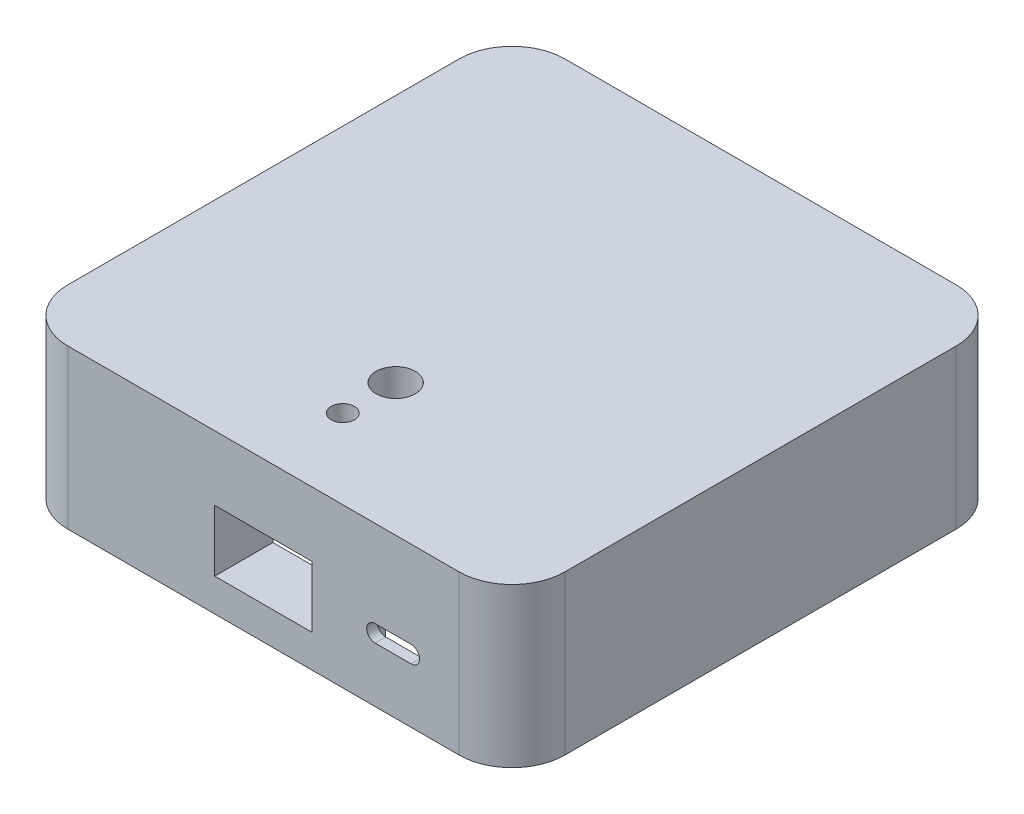
SolidWorks part; units mm, degrees
other "标注1"
sketch "草图24" plane through (-42, 0, -42) normal (-0.1821, -0.7006, -0.6899) x (-0.9631, -0.0142, 0.2687)
ref_plane "前视基准面" through (0, 0, 0) normal (0, 0, 1) x (1, 0, 0)
ref_plane "上视基准面" through (0, 0, 0) normal (0, 1, 0) x (1, 0, 0)
ref_plane "右视基准面" through (0, 0, 0) normal (1, 0, 0) x (0, 0, -1)
sketch "草图1" plane through (0, 0, 0) normal (0, 1, 0) x (1, 0, 0)
  line L1 (47, 47) -> (-47, 47)
  line L2 (47, 47) -> (47, -47)
  line L3 (47, -47) -> (-47, -47)
  line L4 (-47, 47) -> (-47, -47)
  line L5 (47, 47) -> (-47, -47) construction
  line L6 (47, -47) -> (-47, 47) construction
  point P0 (0, 0)
  dimension "D1" = 94
extrude "凸台-拉伸1" add sketch "草图1" along normal blind 30
fillet "圆角1" radius 10 4 edges at (47, 15, 47) (47, 15, -47) (-47, 15, -47) (-47, 15, 47)
shell "抽壳1" thickness 2 removed face at (0, 0, 0)
sketch "草图2" plane through (0, 0, 47) normal (0, 0, 1) x (1, 0, 0)
  line L0 (-37, 30) -> (37, 30) construction
  line L1 (-12.05, 30) -> (12.05, 30)
  line L2 (-12.05, 30) -> (-12.05, 0)
  line L3 (-12.05, 0) -> (12.05, 0)
  line L4 (12.05, 30) -> (12.05, 0)
  line L5 (-12.05, 30) -> (12.05, 0) construction
  line L6 (-12.05, 0) -> (12.05, 30) construction
  line L8 (0, 0) -> (0, 30) construction
  line L9 (-37, 30) -> (37, 30) construction
  point P0 (0, 15)
  point P8 (0, 15)
  dimension "D1" = 24.1
extrude "开关凸台" add sketch "草图2" against normal blind 11
sketch "草图3" plane through (0, 0, 47) normal (0, 0, 1) x (1, 0, 0)
  line L1 (-9.21, 17.8) -> (9.21, 17.8)
  line L2 (-9.21, 17.8) -> (-9.21, 6.2)
  line L3 (-9.21, 6.2) -> (9.21, 6.2)
  line L4 (9.21, 17.8) -> (9.21, 6.2)
  line L5 (-9.21, 17.8) -> (9.21, 6.2) construction
  line L6 (-9.21, 6.2) -> (9.21, 17.8) construction
  point P0 (0, 12)
  dimension "D1" = 18.42
  dimension "D2" = 11.6
  dimension "D3" = 12
extrude "开关切除" cut sketch "草图3" against normal up to next
sketch "草图4" plane through (0, 28, 0) normal (0, -1, 0) x (1, 0, 0)
  line L1 (-12.05, 11.05) -> (12.05, 11.05)
  line L2 (-12.05, 11.05) -> (-12.05, -13.05)
  line L3 (-12.05, -13.05) -> (12.05, -13.05)
  line L4 (12.05, 11.05) -> (12.05, -13.05)
  line L5 (-12.05, 11.05) -> (12.05, -13.05) construction
  line L6 (-12.05, -13.05) -> (12.05, 11.05) construction
  point P0 (0, -1)
  dimension "D1" = 24.1
  dimension "D2" = 1
extrude "触摸切除" cut sketch "草图4" against normal offset from surface (1.4 mm away) 0.6 up to face at (0, 30, 0)
ref_axis "触摸基准轴" through (0, 28, -1) along (0, -1, 0)
sketch "草图6" plane through (0, 28, 0) normal (0, -1, 0) x (1, 0, 0)
  line L0 (-45, -37) -> (-45, -21.6301)
  line L5 (-45, -37) -> (-45, 37) construction
  line L6 (-45, -21.6301) -> (45, -21.6301)
  line L8 (45, 37) -> (45, -37) construction
  line L9 (45, -21.6301) -> (45, -37)
  line L10 (-37, -45) -> (37, -45)
  line L11 (37, -45) -> (-37, -45) construction
  arc A0 (-45, -37) -> (-37, -45) centre (-37, -37) ccw
  arc A1 (37, -45) -> (45, -37) centre (37, -37) ccw
  point P0 (0, -25)
  dimension "D1" = 8
  dimension "D2" = 8
  dimension "D3" = 15.3699
extrude "电池槽基座" add sketch "草图6" along normal blind 14.2
sketch "草图9" plane through (0, 13.8, 0) normal (0, -1, 0) x (1, 0, 0)
  line L0 (-37, -45) -> (37, -45) construction
  line L1 (-34.7, -26.6) -> (34.7, -26.6)
  line L2 (-34.7, -26.6) -> (-34.7, -35.8)
  line L3 (-34.7, -35.8) -> (34.7, -35.8)
  line L4 (34.7, -26.6) -> (34.7, -35.8)
  dimension "D1" = 9.2
  dimension "D2" = 69.4
  dimension "D3" = 9.2
revolve "电池槽切除" cut sketch "草图9" angle 360 about L3
ref_axis "电池槽轴" through (-34.7, 13.8, -35.8) along (1, 0, 0)
sketch "草图10" plane through (0, 28, 0) normal (0, -1, 0) x (1, 0, 0)
  line L1 (-26, 25) -> (26, 25) construction
  line L2 (-26, 25) -> (-26, -11) construction
  line L3 (-26, -11) -> (26, -11) construction
  line L4 (26, 25) -> (26, -11) construction
  line L5 (-26, 25) -> (26, -11) construction
  line L6 (-26, -11) -> (26, 25) construction
  line L7 (-26.5, 25.5) -> (-21.5, 25.5)
  line L8 (-26.5, 25.5) -> (-26.5, 20.5)
  line L9 (-26.5, 20.5) -> (-21.5, 20.5)
  line L10 (-21.5, 25.5) -> (-21.5, 20.5)
  line L11 (-26.5, 25.5) -> (-21.5, 20.5) construction
  line L12 (-26.5, 20.5) -> (-21.5, 25.5) construction
  line L13 (21.5, -6.5) -> (26.5, -6.5)
  line L14 (21.5, -6.5) -> (21.5, -11.5)
  line L15 (21.5, -11.5) -> (26.5, -11.5)
  line L16 (26.5, -6.5) -> (26.5, -11.5)
  line L17 (21.5, -6.5) -> (26.5, -11.5) construction
  line L18 (21.5, -11.5) -> (26.5, -6.5) construction
  point P0 (0, 7)
  point P6 (24, -9)
  point P9 (-24, 23)
  dimension "D1" = 36
  dimension "D2" = 52
  dimension "D3" = 7
  dimension "D4" = 2
  dimension "D5" = 2
  dimension "D6" = 5
  dimension "D7" = 2
  dimension "D8" = 2
  dimension "D9" = 5
extrude "电路板基座" add sketch "草图10" along normal blind 24.19
sketch "草图11" plane through (0, 3.81, 0) normal (0, -1, 0) x (1, 0, 0)
  line L0 (-26.5, 20.5) -> (-21.5, 20.5) construction
  line L1 (-23.0762, 21.4) -> (-22.1525, 23)
  line L2 (-22.1525, 23) -> (-23.0762, 24.6)
  line L3 (-23.0762, 24.6) -> (-24.9238, 24.6)
  line L4 (-24.9238, 24.6) -> (-25.8475, 23)
  line L5 (-25.8475, 23) -> (-24.9238, 21.4)
  line L6 (-24.9238, 21.4) -> (-23.0762, 21.4)
  line L8 (24.9238, -10.6) -> (25.8475, -9)
  line L9 (25.8475, -9) -> (24.9238, -7.4)
  line L10 (24.9238, -7.4) -> (23.0762, -7.4)
  line L11 (23.0762, -7.4) -> (22.1525, -9)
  line L12 (22.1525, -9) -> (23.0762, -10.6)
  line L13 (23.0762, -10.6) -> (24.9238, -10.6)
  line L14 (21.5, -11.5) -> (26.5, -11.5) construction
  circle A0 centre (-24, 23) radius 1.6 construction
  circle A1 centre (24, -9) radius 1.6 construction
  dimension "D1" = 3.2
  dimension "D2" = 3.2
extrude "电路板螺母槽" cut sketch "草图11" against normal blind 4
ref_axis "电路板螺母槽轴-开关" through (-24, 3.81, 23) along (0, -1, 0)
ref_axis "电路板螺母槽轴-电池" through (24, 3.81, -9) along (0, -1, 0)
sketch "草图13" plane through (0, 28, 0) normal (0, -1, 0) x (1, 0, 0)
  line L0 (-45, -37) -> (-45, -16.7681)
  line L5 (-34.7, -45) -> (-37, -45)
  line L16 (-34.7, -16.7681) -> (-34.7, -45)
  line L17 (-34.7, -45) -> (-34.7, -26.6) construction
  line L21 (34.7, -16.7681) -> (34.7, -45)
  line L22 (34.7, -26.6) -> (34.7, -45) construction
  line L28 (34.7, -45) -> (37, -45)
  line L29 (-37, -45) -> (-34.7, -45) construction
  line L30 (-45, 37) -> (-34.7, 37)
  line L31 (-45, 37) -> (-45, 26.7)
  line L32 (-45, 26.7) -> (-34.7, 26.7)
  line L33 (-34.7, 37) -> (-34.7, 26.7)
  line L34 (45, 37) -> (34.7, 37)
  line L35 (45, 37) -> (45, 26.7)
  line L36 (45, 26.7) -> (34.7, 26.7)
  line L37 (34.7, 37) -> (34.7, 26.7)
  line L38 (-45, -21.6301) -> (-45, 37) construction
  line L39 (-45, -16.7681) -> (-34.7, -16.7681)
  line L40 (45, -37) -> (45, -16.7681)
  line L41 (45, -16.7681) -> (34.7, -16.7681)
  arc A1 (-45, -37) -> (-37, -45) centre (-37, -37) ccw
  arc A2 (45, -37) -> (37, -45) centre (37, -37) cw
sketch "草图15" plane through (0, 0, 47) normal (0, 0, 1) x (1, 0, 0)
  line L0 (21.125, 12) -> (27.925, 12) construction
  line L5 (21.125, 13.6) -> (27.925, 13.6)
  line L6 (21.125, 10.4) -> (27.925, 10.4)
  line L7 (9.21, 6.2) -> (9.21, 17.8) construction
  line L8 (12.05, 0) -> (37, 0) construction
  arc A0 (21.125, 13.6) -> (21.125, 10.4) centre (21.125, 12) ccw
  arc A1 (27.925, 10.4) -> (27.925, 13.6) centre (27.925, 12) ccw
  point P2 (24.525, 12)
  point P11 (9.21, 12)
  point P14 (24.525, 0)
  dimension "D2" = 3.2
  dimension "D1" = 6.8
extrude "USBC" cut sketch "草图15" against normal up to next
sketch "草图16" plane through (0, 0, 45) normal (0, 0, -1) x (-1, 0, 0)
  line L0 (-15.225, 13) -> (-16.025, 13)
  line L1 (-16.025, 13) -> (-16.025, 14.6)
  line L2 (-16.025, 14.6) -> (-18.8583, 14.6)
  line L3 (-18.8583, 14.6) -> (-18.8583, 28)
  line L4 (-12.05, 28) -> (-37, 28) construction
  line L5 (-18.8583, 28) -> (-15.225, 28)
  line L6 (-15.225, 28) -> (-15.225, 13)
  line L7 (-24.525, 13.6) -> (-24.525, 28) construction
  line L8 (-27.925, 13.6) -> (-21.125, 13.6) construction
  line L9 (-30.1917, 28) -> (-33.825, 28)
  line L10 (-30.1917, 14.6) -> (-30.1917, 28)
  line L11 (-33.025, 14.6) -> (-30.1917, 14.6)
  line L12 (-33.025, 13) -> (-33.025, 14.6)
  line L13 (-33.825, 13) -> (-33.025, 13)
  line L14 (-33.825, 28) -> (-33.825, 13)
  dimension "D1" = 8.5
  dimension "D2" = 5.6667
  dimension "D3" = 0.8
  dimension "D4" = 1
  dimension "D5" = 1.6
extrude "USBC凸台" add sketch "草图16" along normal blind 26
sketch "草图17" plane through (0, 0, 47) normal (0, 0, 1) x (1, 0, 0)
  line L0 (-37, 0) -> (37, 0) construction
  line L1 (-9.21, 24) -> (9.21, 24)
  line L2 (-9.21, 24) -> (-9.21, 30)
  line L3 (-9.21, 30) -> (9.21, 30)
  line L4 (9.21, 24) -> (9.21, 30)
  line L5 (-9.21, 24) -> (9.21, 30) construction
  line L6 (-9.21, 30) -> (9.21, 24) construction
  line L7 (-37, 30) -> (37, 30) construction
  point P0 (0, 27)
  point P8 (0, 0)
  dimension "D1" = 6
extrude "凸台-拉伸2" [suppressed] add sketch "草图17" along normal blind 3
sketch "草图18" [suppressed] plane through (-6.75, 0, 0) normal (-1, 0, 0) x (0, 0, 1)
  line L0 (45, 25) -> (45, 19)
  arc A0 (45, 19) -> (45, 25) centre (45, 22) ccw
extrude "凸台-拉伸3" [suppressed] add sketch "草图18" against normal up to surface (13.5 mm away)
sketch "草图19" [suppressed] plane through (-6.75, 0, 0) normal (-1, 0, 0) x (0, 0, 1)
  line L1 (45.9238, 20.4) -> (46.8475, 22)
  line L2 (46.8475, 22) -> (45.9238, 23.6)
  line L3 (45.9238, 23.6) -> (44.0762, 23.6)
  line L4 (44.0762, 23.6) -> (43.1525, 22)
  line L5 (43.1525, 22) -> (44.0762, 20.4)
  line L6 (44.0762, 20.4) -> (45.9238, 20.4)
  circle A0 centre (45, 22) radius 1.6 construction
  dimension "D1" = 3.2
extrude "切除-拉伸3" [suppressed] cut sketch "草图19" against normal blind 4
sketch "草图22" plane through (0, 0, 36) normal (0, 0, -1) x (-1, 0, 0)
  line L0 (9.21, 17.8) -> (-9.21, 17.8) construction
  line L1 (12.05, 17.8) -> (-12.05, 17.8)
  line L2 (12.05, 17.8) -> (12.05, 28)
  line L3 (12.05, 28) -> (-12.05, 28)
  line L4 (-12.05, 17.8) -> (-12.05, 28)
  line L5 (-12.05, 28) -> (12.05, 28) construction
  line L6 (-12.05, 0) -> (-12.05, 28) construction
  point P8 (0, 17.8)
extrude "插座凸台" add sketch "草图22" along normal up to surface (24.95 mm away) up to face at (0, 28.7, 11.05)
sketch "草图23" plane through (0, 17.8, 0) normal (0, -1, 0) x (-1, 0, 0)
  line L0 (12.05, -36) -> (-12.05, -36) construction
  circle A0 centre (0, -32) radius 2.2
  circle A1 centre (0, -22) radius 3.7
  dimension "D1" = 7.4
  dimension "D2" = 4.4
  dimension "D3" = 10
  dimension "D4" = 4
extrude "切除-拉伸6" cut sketch "草图23" against normal up to next
ref_axis "电路板轴-电池" through (24, 3.81, -9) along (0, -1, 0)
ref_axis "电池板轴-开关" through (-24, 3.81, 23) along (0, -1, 0)
extrude "凸台-拉伸4" add sketch "草图13" along normal up to surface (28 mm away) up to face at (0, 0, 0)
sketch "草图25" plane through (0, 0, 0) normal (0, -1, 0) x (1, 0, 0)
  line L0 (-37.85, -25) -> (-38.85, -26.7321)
  line L13 (39.85, -25) -> (-39.85, -25) construction
  line L14 (39.85, -25) -> (39.85, 31.85) construction
  line L15 (39.85, 31.85) -> (-39.85, 31.85) construction
  line L16 (-39.85, -25) -> (-39.85, 31.85) construction
  line L17 (39.85, -25) -> (-39.85, 31.85) construction
  line L18 (39.85, 31.85) -> (-39.85, -25) construction
  line L19 (-38.85, 30.1179) -> (-37.85, 31.85)
  line L20 (-37.85, 31.85) -> (-38.85, 33.5821)
  line L21 (-38.85, 33.5821) -> (-40.85, 33.5821)
  line L22 (-40.85, 33.5821) -> (-41.85, 31.85)
  line L23 (-41.85, 31.85) -> (-40.85, 30.1179)
  line L24 (-40.85, 30.1179) -> (-38.85, 30.1179)
  line L25 (-38.85, -26.7321) -> (-37.85, -25)
  line L26 (-37.85, -25) -> (-38.85, -23.2679)
  line L27 (-38.85, -23.2679) -> (-40.85, -23.2679)
  line L28 (-40.85, -23.2679) -> (-41.85, -25)
  line L29 (-41.85, -25) -> (-40.85, -26.7321)
  line L30 (-40.85, -26.7321) -> (-38.85, -26.7321)
  line L31 (-38.85, -23.2679) -> (-37.85, -25)
  line L32 (-41.85, -25) -> (-40.85, -23.2679)
  line L33 (-40.85, -26.7321) -> (-41.85, -25)
  line L34 (-37.85, 31.85) -> (-38.85, 30.1179)
  line L35 (-38.85, 33.5821) -> (-37.85, 31.85)
  line L36 (-41.85, 31.85) -> (-40.85, 33.5821)
  line L37 (-40.85, 30.1179) -> (-41.85, 31.85)
  line L38 (-38.85, 30.1179) -> (-37.85, 31.85)
  line L39 (-37.85, 31.85) -> (-38.85, 33.5821)
  line L40 (-40.85, 33.5821) -> (-41.85, 31.85)
  line L41 (-41.85, 31.85) -> (-40.85, 30.1179)
  line L42 (-38.85, -26.7321) -> (-37.85, -25)
  line L43 (-37.85, -25) -> (-38.85, -23.2679)
  line L44 (-40.85, -23.2679) -> (-41.85, -25)
  line L45 (-37.85, -25) -> (-38.85, -26.7321)
  line L46 (-38.85, -23.2679) -> (-37.85, -25)
  line L47 (-41.85, -25) -> (-40.85, -23.2679)
  line L48 (-40.85, -26.7321) -> (-41.85, -25)
  line L49 (-37.85, 31.85) -> (-38.85, 30.1179)
  line L50 (-38.85, 33.5821) -> (-37.85, 31.85)
  line L51 (-41.85, 31.85) -> (-40.85, 33.5821)
  line L52 (-40.85, 30.1179) -> (-41.85, 31.85)
  line L53 (-41.85, -25) -> (-40.85, -26.7321)
  line L54 (0, -16.5) -> (0, 16.5) construction
  line L55 (37.85, -25) -> (38.85, -23.2679)
  line L56 (37.85, -25) -> (38.85, -26.7321)
  line L57 (40.85, -26.7321) -> (38.85, -26.7321)
  line L58 (41.85, -25) -> (40.85, -26.7321)
  line L59 (40.85, -23.2679) -> (41.85, -25)
  line L60 (38.85, -23.2679) -> (40.85, -23.2679)
  line L61 (37.85, 31.85) -> (38.85, 33.5821)
  line L62 (38.85, 30.1179) -> (37.85, 31.85)
  line L63 (40.85, 30.1179) -> (38.85, 30.1179)
  line L64 (41.85, 31.85) -> (40.85, 30.1179)
  line L65 (40.85, 33.5821) -> (41.85, 31.85)
  line L66 (38.85, 33.5821) -> (40.85, 33.5821)
  circle A0 centre (-39.85, 31.85) radius 1.7321 construction
  circle A1 centre (-39.85, -25) radius 1.7321 construction
  point P0 (0, 3.425)
  dimension "D4" = 2
  dimension "D5" = 2
  dimension "D1" = 56.85
  dimension "D2" = 79.7
  dimension "D3" = 25
sketch "草图26" plane through (0, 0, 0) normal (0, -1, 0) x (1, 0, 0)
  line L0 (-40.85, 30.1179) -> (-38.85, 30.1179) construction
  line L1 (-38.85, 30.1179) -> (-37.85, 31.85) construction
  line L2 (-37.85, 31.85) -> (-38.85, 33.5821) construction
  line L3 (-38.85, 33.5821) -> (-40.85, 33.5821) construction
  line L4 (-40.85, 33.5821) -> (-41.85, 31.85) construction
  line L5 (-41.85, 31.85) -> (-40.85, 30.1179) construction
  line L6 (40.85, 33.5821) -> (41.85, 31.85) construction
  line L7 (41.85, 31.85) -> (40.85, 30.1179) construction
  line L8 (40.85, 30.1179) -> (38.85, 30.1179) construction
  line L9 (38.85, 30.1179) -> (37.85, 31.85) construction
  line L10 (37.85, 31.85) -> (38.85, 33.5821) construction
  line L11 (38.85, 33.5821) -> (40.85, 33.5821) construction
  line L12 (40.85, -23.2679) -> (41.85, -25) construction
  line L13 (38.85, -23.2679) -> (40.85, -23.2679) construction
  line L14 (37.85, -25) -> (38.85, -23.2679) construction
  line L15 (37.85, -25) -> (38.85, -26.7321) construction
  line L16 (40.85, -26.7321) -> (38.85, -26.7321) construction
  line L17 (41.85, -25) -> (40.85, -26.7321) construction
  line L18 (-40.85, -23.2679) -> (-41.85, -25) construction
  line L19 (-41.85, -25) -> (-40.85, -26.7321) construction
  line L20 (-40.85, -26.7321) -> (-38.85, -26.7321) construction
  line L21 (-37.85, -25) -> (-38.85, -26.7321) construction
  line L22 (-37.85, -25) -> (-38.85, -23.2679) construction
  line L23 (-38.85, -23.2679) -> (-40.85, -23.2679) construction
  line L24 (-40.85, 30.1179) -> (-38.85, 30.1179)
  line L25 (-38.85, 30.1179) -> (-37.85, 31.85)
  line L26 (-37.85, 31.85) -> (-38.85, 33.5821)
  line L27 (-38.85, 33.5821) -> (-40.85, 33.5821)
  line L28 (-40.85, 33.5821) -> (-41.85, 31.85)
  line L29 (-41.85, 31.85) -> (-40.85, 30.1179)
  line L30 (40.85, 33.5821) -> (41.85, 31.85)
  line L31 (41.85, 31.85) -> (40.85, 30.1179)
  line L32 (40.85, 30.1179) -> (38.85, 30.1179)
  line L33 (38.85, 30.1179) -> (37.85, 31.85)
  line L34 (37.85, 31.85) -> (38.85, 33.5821)
  line L35 (38.85, 33.5821) -> (40.85, 33.5821)
  line L36 (40.85, -23.2679) -> (41.85, -25)
  line L37 (38.85, -23.2679) -> (40.85, -23.2679)
  line L38 (37.85, -25) -> (38.85, -23.2679)
  line L39 (37.85, -25) -> (38.85, -26.7321)
  line L40 (40.85, -26.7321) -> (38.85, -26.7321)
  line L41 (41.85, -25) -> (40.85, -26.7321)
  line L42 (-40.85, -23.2679) -> (-41.85, -25)
  line L43 (-41.85, -25) -> (-40.85, -26.7321)
  line L44 (-40.85, -26.7321) -> (-38.85, -26.7321)
  line L45 (-37.85, -25) -> (-38.85, -26.7321)
  line L46 (-37.85, -25) -> (-38.85, -23.2679)
  line L47 (-38.85, -23.2679) -> (-40.85, -23.2679)
extrude "切除-拉伸7" cut sketch "草图26" against normal blind 4
equation "\"squ_side\"= 94mm"
equation "\"D1@草图1\"=\"squ_side\""
equation "\"squ_high\"= 30mm"
equation "\"D1@凸台-拉伸1\"=\"squ_high\""
equation "\"squ_corner\"= 10mm"
equation "\"D1@圆角1\"=\"squ_corner\""
equation "\"squ_thickness\"= 2.0mm"
equation "\"D1@抽壳1\"=\"squ_thickness\""
equation "\"sw_thickness\"= 11mm"
equation "\"sw_width\"= 18.42mm"
equation "\"sw_high\"= 11.6mm"
equation "\"D1@开关凸台\" = \"sw_thickness\""
equation "\"D1@草图3\"=\"sw_width\""
equation "\"D2@草图3\"=\"sw_high\""
equation "\"touch_thickness\"= 0.6mm"
equation "\"touch_side\"= 23.6mm"
equation "\"D1@草图4\"=\"touch_side\"+0.5mm"
equation "\"battery_diameter\"= 18.4mm"
equation "\"battery_length\"= 66.4mm"
equation "\"battery_thickness\"= 0.8mm"
equation "\"D1@电池槽基座\"=\"battery_diameter\" / 2+5mm"
equation "\"D1@草图9\"=\"battery_diameter\"/2"
equation "\"conch_length\"= 52mm"
equation "\"conch_width\"= 36mm"
equation "\"D1@草图10\"=\"conch_width\""
equation "\"D2@草图10\"=\"conch_length\""
equation "\"nut_side\"= 2.8mm"
equation "\"nut_distance\"= 2mm"
equation "\"D4@草图10\"=\"nut_distance\""
equation "\"D5@草图10\"=\"nut_distance\""
equation "\"nut_squ\"= 5mm"
equation "\"D6@草图10\"=\"nut_squ\""
equation "\"D7@草图10\"=\"nut_distance\""
equation "\"D8@草图10\"=\"nut_distance\""
equation "\"D9@草图10\"=\"nut_squ\""
equation "\"conch_high\"= 6.19mm"
equation "\"D1@电路板基座\"=\"conch_high\" + 18mm"
equation "\"nut_high\"= 4mm"
equation "\"D1@电路板螺母槽\" = \"nut_high\""
equation "\"nut_side_err\"= \"nut_side\" + 0.4mm"
equation "\"D1@草图11\"=\"nut_side_err\""
equation "\"D2@草图11\"=\"nut_side_err\""
equation "\"bottom_length\"= 30mm"
equation "\"bottom_width\"= 25mm"
equation "\"battery_length_err\"= \"battery_length\" + 3.0mm"
equation "\"D2@草图9\"=\"battery_length_err\""
equation "\"usbc_high\"= 3.2mm"
equation "\"usbc_corner_radius_90\"= 1.25mm"
equation "\"usbc_corner_radius_err\"= \"usbc_corner_radius_90\" + 0.4mm"
equation "\"usbc_length\"= 6.8mm"
equation "\"D1@草图15\"=\"usbc_length\""
equation "\"D2@草图15\"=\"usbc_high\""
equation "\"usb_board_width\"= 17mm"
equation "\"usb_board_length\"= 26mm"
equation "\"D1@草图16\"=\"usb_board_width\"/2"
equation "\"D2@草图16\"=\"usb_board_width\"/3"
equation "\"D1@USBC凸台\"=\"usb_board_length\""
equation "\"D1@切除-拉伸3\"=\"nut_high\""
equation "\"socket_big\"= 7.4mm"
equation "\"socket_small\"= 4.4mm"
equation "\"D1@草图23\"=\"socket_big\""
equation "\"D2@草图23\"=\"socket_small\""
equation "\"socket_distance\"= 10mm"
equation "\"D3@草图23\"=\"socket_distance\""
equation "\"D1@触摸切除\"=\"touch_thickness\""
equation "\"squ_radius\"= 8mm"
equation "\"D3@草图9\"=\"battery_diameter\"/2"
equation "\"25、\"=5.83818"
equation "\"D4@草图25\"=\"nut_distance\""
equation "\"D5@草图25\"=\"nut_distance\""
equation "\"D1@切除-拉伸7\"=\"nut_high\""
